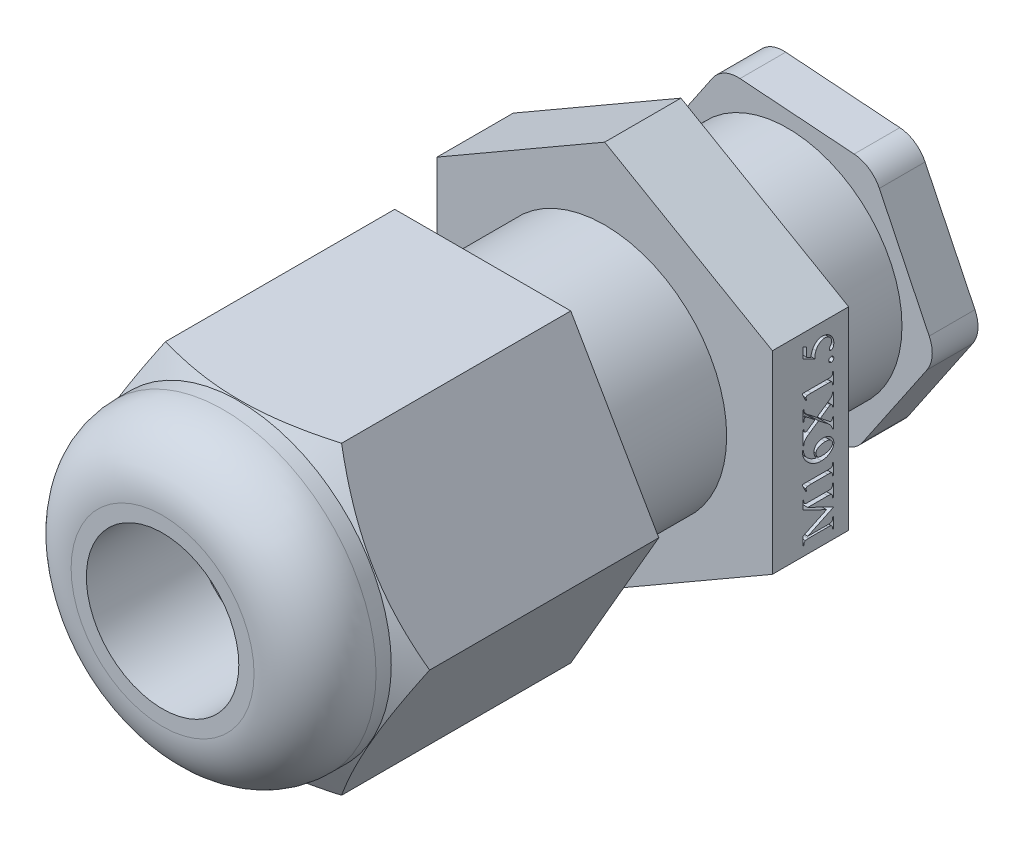
SolidWorks part; units mm, degrees
ref_plane "Front Plane" through (0, 0, 0) normal (0, 0, 1) x (1, 0, 0)
ref_plane "Top Plane" through (0, 0, 0) normal (0, 1, 0) x (1, 0, 0)
ref_plane "Right Plane" through (0, 0, 0) normal (1, 0, 0) x (0, 0, -1)
sketch "Sketch2" plane through (0, 0, 0) normal (0, 0, 1) x (1, 0, 0)
  line L1 (-299.5259, 272.6716) -> (420.4741, 272.6716) construction
sketch "Sketch16" plane through (0, 0, 0) normal (0, 0, 1) x (1, 0, 0)
  circle A0 centre (0, 0) radius 7.5
  dimension "D1" = 15
extrude "Boss-Extrude1" add sketch "Sketch16" along normal blind 5
sketch "Sketch17" plane through (0, 0, 5) normal (0, 0, 1) x (1, 0, 0)
  line L1 (12.7017, 0) -> (6.3509, 11)
  line L2 (6.3509, 11) -> (-6.3509, 11)
  line L3 (-6.3509, 11) -> (-12.7017, 0)
  line L4 (-12.7017, 0) -> (-6.3509, -11)
  line L5 (-6.3509, -11) -> (6.3509, -11)
  line L6 (6.3509, -11) -> (12.7017, 0)
  circle A0 centre (0, 0) radius 11 construction
  dimension "D1" = 22
extrude "Boss-Extrude2" add sketch "Sketch17" along normal blind 4
sketch "Sketch18" plane through (0, 0, 9) normal (0, 0, 1) x (1, 0, 0)
  circle A0 centre (0, 0) radius 9
  dimension "D1" = 18
extrude "Boss-Extrude3" add sketch "Sketch18" along normal blind 1
sketch "Sketch19" plane through (0, 0, 10) normal (0, 0, 1) x (1, 0, 0)
  circle A0 centre (0, 0) radius 7.5
  dimension "D1" = 15
extrude "Boss-Extrude4" add sketch "Sketch19" along normal blind 5
sketch "Sketch20" plane through (0, 0, 15) normal (0, 0, 1) x (1, 0, 0)
  line L1 (0, 12.7017) -> (-11, 6.3509)
  line L2 (-11, 6.3509) -> (-11, -6.3509)
  line L3 (-11, -6.3509) -> (0, -12.7017)
  line L4 (0, -12.7017) -> (11, -6.3509)
  line L5 (11, -6.3509) -> (11, 6.3509)
  line L6 (11, 6.3509) -> (0, 12.7017)
  circle A0 centre (0, 0) radius 11 construction
  dimension "D1" = 22
extrude "Boss-Extrude5" add sketch "Sketch20" along normal blind 5
sketch "Sketch21" plane through (0, 0, 20) normal (0, 0, 1) x (1, 0, 0)
  circle A0 centre (0, 0) radius 8
  dimension "D1" = 16
extrude "Boss-Extrude6" add sketch "Sketch21" along normal blind 8
sketch "Sketch22" plane through (0, 0, 28) normal (0, 0, 1) x (1, 0, 0)
  line L1 (-11.547, 0) -> (-5.7735, -10)
  line L2 (-5.7735, -10) -> (5.7735, -10)
  line L3 (5.7735, -10) -> (11.547, 0)
  line L4 (11.547, 0) -> (5.7735, 10)
  line L5 (5.7735, 10) -> (-5.7735, 10)
  line L6 (-5.7735, 10) -> (-11.547, 0)
  circle A0 centre (0, 0) radius 10 construction
  dimension "D1" = 20
extrude "Boss-Extrude7" add sketch "Sketch22" along normal blind 16
sketch "Sketch24" plane through (0, 0, 44) normal (0, 0, 1) x (1, 0, 0)
  circle A0 centre (0, 0) radius 10
  dimension "D1" = 20
extrude "Boss-Extrude8" add sketch "Sketch24" along normal blind 5
sketch "Sketch25" plane through (0, 0, 49) normal (0, 0, 1) x (1, 0, 0)
  circle A0 centre (0, 0) radius 5
  dimension "D1" = 10
extrude "Cut-Extrude1" cut sketch "Sketch25" against normal blind 12
sketch "Sketch26" plane through (0, 0, 0) normal (0, 0, -1) x (-1, 0, 0)
  circle A0 centre (0, 0) radius 6.75
  dimension "D1" = 13.5
extrude "Cut-Extrude2" cut sketch "Sketch26" against normal blind 42
fillet "Fillet1" radius 4 1 edges at (10, 0, 49)
sketch "Sketch29" plane through (0, 0, 44) normal (0, 0, 1) x (1, 0, 0)
  circle A0 centre (0, 0) radius 9.873
  circle A1 centre (0, 0) radius 9.873 construction
  circle A2 centre (0, 0) radius 19.2648
extrude "Cut-Extrude6" cut sketch "Sketch29" against normal blind 11 draft 60
sketch "Sketch30" plane through (0, 0, 5) normal (0, 0, -1) x (-1, 0, 0)
  line L0 (-12.7017, 0) -> (-6.3509, 11) construction
  circle A0 centre (0, 0) radius 11
  circle A1 centre (0, 0) radius 18.6783
extrude "Cut-Extrude7" cut sketch "Sketch30" against normal blind 10.7366 draft 60
sketch "Sketch31" plane through (11, 0, 0) normal (1, 0, 0) x (0, 0, -1)
  line L0 (-16, -6.3509) -> (-16, 6.3509) construction
  line L3 (-15, -7.5) -> (-15, 7.5) construction
  text T0 "M16X1.5" font "Times New Roman" height 2
  dimension "D1" = 1
extrude "Cut-Extrude8" cut sketch "Sketch31" against normal blind 1
sketch "Sketch32" plane through (-11, 0, 0) normal (-1, 0, 0) x (0, 0, 1)
  line L0 (16, 6.3509) -> (16, -6.3509) construction
  line L1 (20, 6.3509) -> (15, 6.3509) construction
  line L2 (20, -6.3509) -> (15, -6.3509) construction
  line L3 (15, 6.3509) -> (15, -6.3509) construction
  text T0 "СЄ" font "Arial" height 3.5
  dimension "D1" = 1
extrude "Cut-Extrude9" cut sketch "Sketch32" against normal blind 1
sketch "Эскиз1" plane through (0, 0, 0) normal (0, 0, -1) x (-1, 0, 0)
  circle A0 centre (0, 0) radius 14.1977
sketch "Эскиз2" plane through (0, 0, 5) normal (0, 0, -1) x (-1, 0, 0)
  line L1 (4.2776, 8.8338) -> (-5.5115, 8.1214)
  line L2 (-5.5115, 8.1214) -> (-9.7891, -0.7124)
  line L3 (-9.7891, -0.7124) -> (-4.2776, -8.8338)
  line L4 (-4.2776, -8.8338) -> (5.5115, -8.1214)
  line L5 (5.5115, -8.1214) -> (9.7891, 0.7124)
  line L6 (9.7891, 0.7124) -> (4.2776, 8.8338)
  circle A0 centre (0, 0) radius 8.5 construction
  dimension "D1" = 17
extrude "Вырез-Вытянуть2" cut sketch "Эскиз2" along direction (0, 0, 1) on the side against the normal blind 4 flip side to cut
sketch "Эскиз3" plane through (0, 0, 10) normal (0, 0, 1) x (1, 0, 0)
  circle A0 centre (0, 0) radius 18.1876
  circle A1 centre (0, 0) radius 7.5
  dimension "D1" = 15
extrude "Вырез-Вытянуть5" cut sketch "Эскиз3" against normal blind 2
extrude "Вырез-Вытянуть6" cut sketch "Эскиз1" against normal blind 5
fillet "Скругление1" radius 2 6 edges at (9.7891, -0.7124, 6.5) (4.2776, -8.8338, 6.5) (-5.5115, -8.1214, 6.5) (-9.7891, 0.7124, 6.5) (-4.2776, 8.8338, 6.5) (5.5115, 8.1214, 6.5)
